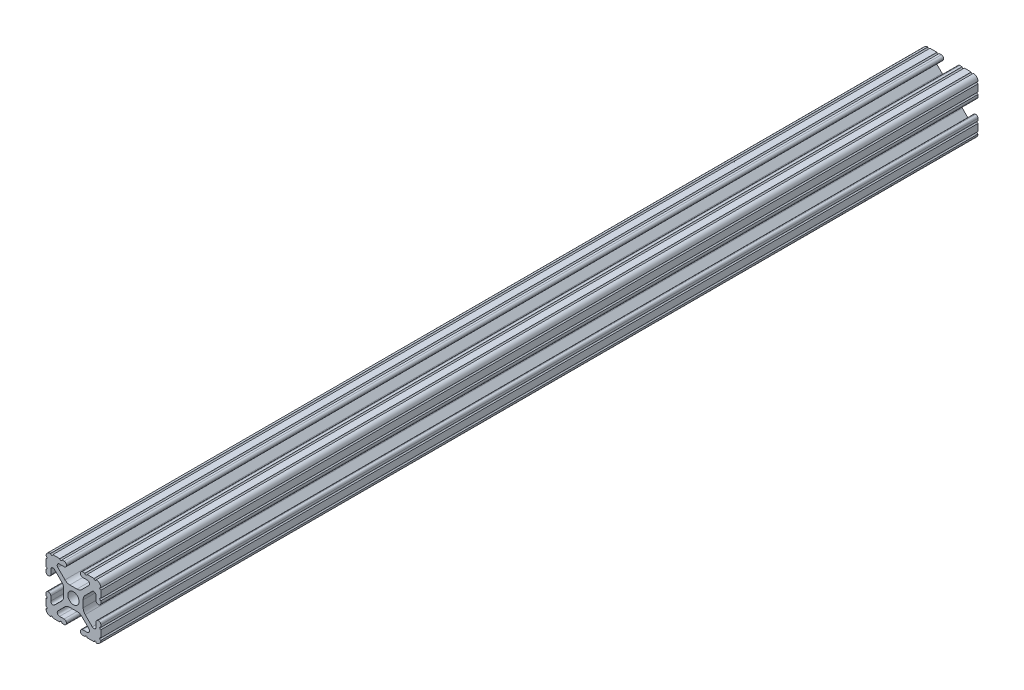
SolidWorks part; units mm, degrees
ref_plane "Front Plane" through (0, 0, 0) normal (0, 0, 1) x (1, 0, 0)
ref_plane "Top Plane" through (0, 0, 0) normal (0, 1, 0) x (1, 0, 0)
ref_plane "Right Plane" through (0, 0, 0) normal (1, 0, 0) x (0, 0, -1)
sketch "Sketch1" plane through (0, 0, 0) normal (0, 0, 1) x (1, 0, 0)
  line L88 (-7.1797, -8.6452) -> (-3.9523, -5.4237)
  line L89 (-1.7093, -4.4958) -> (1.7093, -4.4958)
  line L90 (3.9523, -5.4237) -> (7.1797, -8.6452)
  line L91 (6.4164, -10.4902) -> (4.2875, -10.4902)
  line L92 (3.2385, -11.5392) -> (3.2385, -11.651)
  line L93 (4.2875, -12.7) -> (5.3171, -12.7)
  line L94 (6.3331, -12.7) -> (9.5504, -12.7)
  line L95 (12.7, -9.5504) -> (12.7, -6.3331)
  line L96 (12.7, -5.3171) -> (12.7, -4.2875)
  line L97 (11.651, -3.2385) -> (11.5392, -3.2385)
  line L98 (10.4902, -4.2875) -> (10.4902, -6.4021)
  line L99 (8.7371, -7.1294) -> (5.441, -3.8408)
  line L100 (4.5085, -1.5932) -> (4.5085, 1.5932)
  line L101 (5.441, 3.8408) -> (8.7371, 7.1294)
  line L102 (10.4902, 6.4021) -> (10.4902, 4.2875)
  line L103 (11.5392, 3.2385) -> (11.651, 3.2385)
  line L104 (12.7, 4.2875) -> (12.7, 5.3171)
  line L105 (12.7, 6.3331) -> (12.7, 9.5504)
  line L106 (9.5504, 12.7) -> (6.3331, 12.7)
  line L107 (5.3171, 12.7) -> (4.2875, 12.7)
  line L108 (3.2385, 11.651) -> (3.2385, 11.5392)
  line L109 (4.2875, 10.4902) -> (6.4768, 10.4902)
  line L110 (7.207, 8.7244) -> (3.8983, 5.4232)
  line L111 (1.6558, 4.4958) -> (-1.6558, 4.4958)
  line L112 (-3.8983, 5.4232) -> (-7.207, 8.7244)
  line L113 (-6.4768, 10.4902) -> (-4.2875, 10.4902)
  line L114 (-3.2385, 11.5392) -> (-3.2385, 11.651)
  line L115 (-4.2875, 12.7) -> (-5.3171, 12.7)
  line L116 (-6.3331, 12.7) -> (-9.5504, 12.7)
  line L117 (-12.7, 9.5504) -> (-12.7, 6.3331)
  line L118 (-12.7, 5.3171) -> (-12.7, 4.2875)
  line L119 (-11.651, 3.2385) -> (-11.5392, 3.2385)
  line L120 (-10.4902, 4.2875) -> (-10.4902, 6.4021)
  line L121 (-8.7371, 7.1294) -> (-5.441, 3.8408)
  line L122 (-4.5085, 1.5932) -> (-4.5085, -1.5932)
  line L123 (-5.441, -3.8408) -> (-8.7371, -7.1294)
  line L124 (-10.4902, -6.4021) -> (-10.4902, -4.2875)
  line L125 (-11.5392, -3.2385) -> (-11.651, -3.2385)
  line L126 (-12.7, -4.2875) -> (-12.7, -5.3171)
  line L127 (-12.7, -6.3331) -> (-12.7, -9.5504)
  line L128 (-9.5504, -12.7) -> (-6.3331, -12.7)
  line L129 (-5.3171, -12.7) -> (-4.2875, -12.7)
  line L130 (-3.2385, -11.651) -> (-3.2385, -11.5392)
  line L131 (-4.2875, -10.4902) -> (-6.4164, -10.4902)
  circle A1 centre (0, 0) radius 2.6035
  arc A104 (-7.1797, -8.6452) -> (-6.4164, -10.4902) centre (-6.4164, -9.4098) ccw
  arc A105 (-1.7093, -4.4958) -> (-3.9523, -5.4237) centre (-1.7093, -7.6708) ccw
  arc A106 (3.9523, -5.4237) -> (1.7093, -4.4958) centre (1.7093, -7.6708) ccw
  arc A107 (6.4164, -10.4902) -> (7.1797, -8.6452) centre (6.4164, -9.4098) ccw
  arc A108 (4.2875, -10.4902) -> (3.2385, -11.5392) centre (4.2875, -11.5392) ccw
  arc A109 (3.2385, -11.651) -> (4.2875, -12.7) centre (4.2875, -11.651) ccw
  arc A110 (6.3331, -12.7) -> (5.3171, -12.7) centre (5.8251, -12.7) ccw
  arc A111 (10.5664, -12.6998) -> (9.5504, -12.7) centre (10.0584, -12.7) ccw
  arc A112 (10.5664, -12.6998) -> (12.6998, -10.5664) centre (10.5918, -10.5918) ccw
  arc A113 (12.7, -9.5504) -> (12.6998, -10.5664) centre (12.7, -10.0584) ccw
  arc A114 (12.7, -5.3171) -> (12.7, -6.3331) centre (12.7, -5.8251) ccw
  arc A115 (12.7, -4.2875) -> (11.651, -3.2385) centre (11.651, -4.2875) ccw
  arc A116 (11.5392, -3.2385) -> (10.4902, -4.2875) centre (11.5392, -4.2875) ccw
  arc A117 (8.7371, -7.1294) -> (10.4902, -6.4021) centre (9.4628, -6.4021) ccw
  arc A118 (4.5085, -1.5932) -> (5.441, -3.8408) centre (7.6835, -1.5932) ccw
  arc A119 (5.441, 3.8408) -> (4.5085, 1.5932) centre (7.6835, 1.5932) ccw
  arc A120 (10.4902, 6.4021) -> (8.7371, 7.1294) centre (9.4628, 6.4021) ccw
  arc A121 (10.4902, 4.2875) -> (11.5392, 3.2385) centre (11.5392, 4.2875) ccw
  arc A122 (11.651, 3.2385) -> (12.7, 4.2875) centre (11.651, 4.2875) ccw
  arc A123 (12.7, 6.3331) -> (12.7, 5.3171) centre (12.7, 5.8251) ccw
  arc A124 (12.6998, 10.5664) -> (12.7, 9.5504) centre (12.7, 10.0584) ccw
  arc A125 (12.6998, 10.5664) -> (10.5664, 12.6998) centre (10.5918, 10.5918) ccw
  arc A126 (9.5504, 12.7) -> (10.5664, 12.6998) centre (10.0584, 12.7) ccw
  arc A127 (5.3171, 12.7) -> (6.3331, 12.7) centre (5.8251, 12.7) ccw
  arc A128 (4.2875, 12.7) -> (3.2385, 11.651) centre (4.2875, 11.651) ccw
  arc A129 (3.2385, 11.5392) -> (4.2875, 10.4902) centre (4.2875, 11.5392) ccw
  arc A130 (7.207, 8.7244) -> (6.4768, 10.4902) centre (6.4768, 9.4563) ccw
  arc A131 (1.6558, 4.4958) -> (3.8983, 5.4232) centre (1.6558, 7.6708) ccw
  arc A132 (-3.8983, 5.4232) -> (-1.6558, 4.4958) centre (-1.6558, 7.6708) ccw
  arc A133 (-6.4768, 10.4902) -> (-7.207, 8.7244) centre (-6.4768, 9.4563) ccw
  arc A134 (-4.2875, 10.4902) -> (-3.2385, 11.5392) centre (-4.2875, 11.5392) ccw
  arc A135 (-3.2385, 11.651) -> (-4.2875, 12.7) centre (-4.2875, 11.651) ccw
  arc A136 (-6.3331, 12.7) -> (-5.3171, 12.7) centre (-5.8251, 12.7) ccw
  arc A137 (-10.5664, 12.6998) -> (-9.5504, 12.7) centre (-10.0584, 12.7) ccw
  arc A138 (-10.5664, 12.6998) -> (-12.6998, 10.5664) centre (-10.5918, 10.5918) ccw
  arc A139 (-12.7, 9.5504) -> (-12.6998, 10.5664) centre (-12.7, 10.0584) ccw
  arc A140 (-12.7, 5.3171) -> (-12.7, 6.3331) centre (-12.7, 5.8251) ccw
  arc A141 (-12.7, 4.2875) -> (-11.651, 3.2385) centre (-11.651, 4.2875) ccw
  arc A142 (-11.5392, 3.2385) -> (-10.4902, 4.2875) centre (-11.5392, 4.2875) ccw
  arc A143 (-8.7371, 7.1294) -> (-10.4902, 6.4021) centre (-9.4628, 6.4021) ccw
  arc A144 (-4.5085, 1.5932) -> (-5.441, 3.8408) centre (-7.6835, 1.5932) ccw
  arc A145 (-5.441, -3.8408) -> (-4.5085, -1.5932) centre (-7.6835, -1.5932) ccw
  arc A146 (-10.4902, -6.4021) -> (-8.7371, -7.1294) centre (-9.4628, -6.4021) ccw
  arc A147 (-10.4902, -4.2875) -> (-11.5392, -3.2385) centre (-11.5392, -4.2875) ccw
  arc A148 (-11.651, -3.2385) -> (-12.7, -4.2875) centre (-11.651, -4.2875) ccw
  arc A149 (-12.7, -6.3331) -> (-12.7, -5.3171) centre (-12.7, -5.8251) ccw
  arc A150 (-12.6998, -10.5664) -> (-12.7, -9.5504) centre (-12.7, -10.0584) ccw
  arc A151 (-12.6998, -10.5664) -> (-10.5664, -12.6998) centre (-10.5918, -10.5918) ccw
  arc A152 (-9.5504, -12.7) -> (-10.5664, -12.6998) centre (-10.0584, -12.7) ccw
  arc A153 (-5.3171, -12.7) -> (-6.3331, -12.7) centre (-5.8251, -12.7) ccw
  arc A154 (-4.2875, -12.7) -> (-3.2385, -11.651) centre (-4.2875, -11.651) ccw
  arc A155 (-3.2385, -11.5392) -> (-4.2875, -10.4902) centre (-4.2875, -11.5392) ccw
extrude "Boss-Extrude1" add sketch "Sketch1" along normal mid plane 406.4
equation "\"deep\"= 6in"
equation "\"high\"= 24in"
equation "\"wide\"= 14in"
equation "\"Length@Boss-Extrude1\"  = \"front wide\""
equation "\"front wide\"= 16in"
